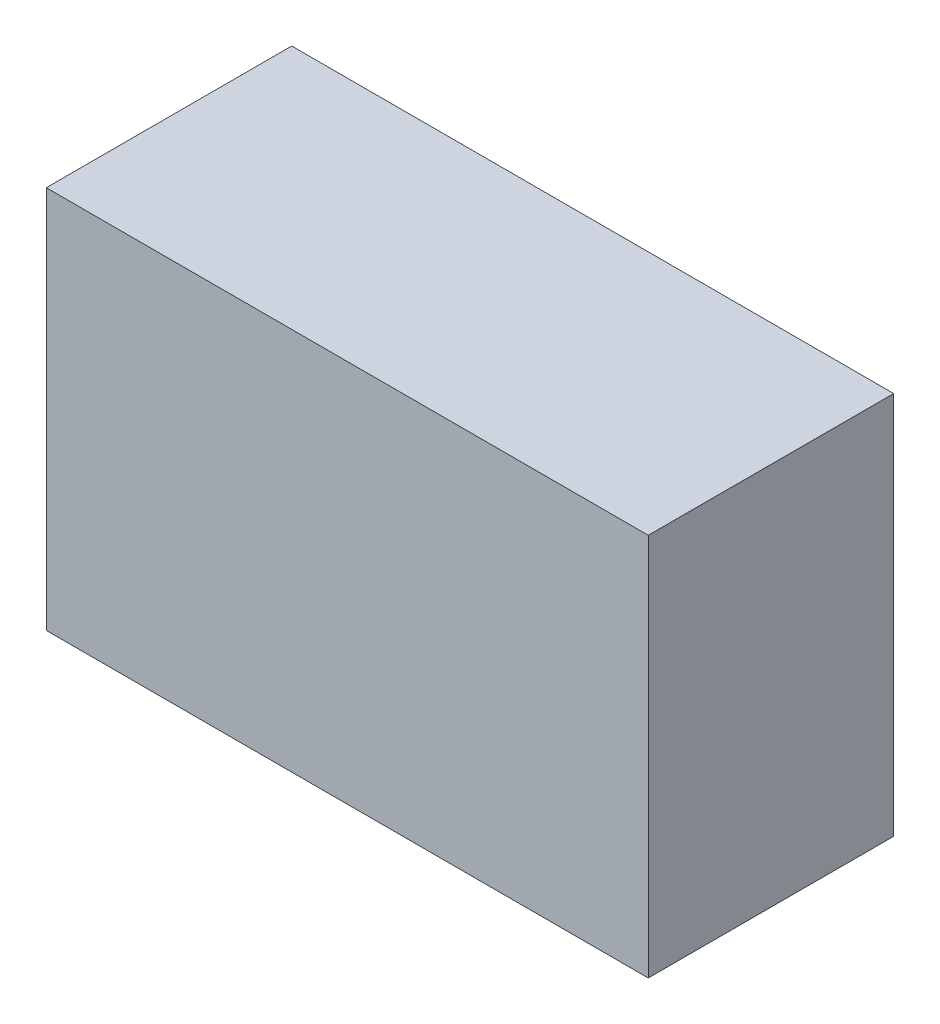
SolidWorks part; units mm, degrees
material "1060 Alloy"
ref_plane "Front" through (0, 0, 0) normal (0, 0, 1) x (1, 0, 0)
ref_plane "Top" through (0, 0, 0) normal (0, 1, 0) x (1, 0, 0)
ref_plane "Right" through (0, 0, 0) normal (1, 0, 0) x (0, 0, -1)
sketch "Sketch3" plane through (0, 0, 0) normal (0, 0, 1) x (1, 0, 0)
  line L0 (-0.127, -6.35) -> (30.1755, -6.35)
  line L1 (0, 0) -> (31.1484, 0)
  line L2 (0, 0) -> (0, -19.8376)
  line L3 (0, -19.8376) -> (31.1484, -19.8376)
  line L4 (31.1484, 0) -> (31.1484, -19.8376)
  line L5 (15.5742, -19.8376) -> (15.5742, 0) construction
  line L6 (15.5742, -6.35) -> (8.0621, -19.3614) construction
  line L15 (12.5496, -11.5887) -> (15.5742, -13.335) construction
  line L16 (15.5742, -6.35) -> (22.9274, -19.0862) construction
  circle A0 centre (15.5742, -6.35) radius 6.0492 construction
  point P14 (0, -6.35)
  point P17 (9.525, -6.35)
  point P19 (31.1484, -6.35)
  point P20 (7.7871, -19.8376)
  point P24 (23.3613, -19.8376)
  dimension "D2" = 6.35
  dimension "D6" = 3.4925
  dimension "D3" = 60
  dimension "D1" = 9.525
  dimension "D4" = 9.525
  dimension "D5" = 60
extrude "Boss-Extrude1" add sketch "Sketch3" along normal mid plane 12.7
sketch "Sketch4" plane through (0, 0, 0) normal (-1, 0, 0) x (0, 0, 1)
  circle A0 centre (0, -6.35) radius 3.175
  dimension "D1" = 6.35
extrude "Cut-Extrude1" cut sketch "Sketch4" against normal blind 9.525
ref_plane "Plane1" through (7.7871, -19.8376, 0) normal (-0.5, -0.866, 0) x (-0.866, 0.5, 0)
ref_plane "Mirror Plane" through (15.5742, 0, 0) normal (-1, 0, 0) x (0, 0, 1)
sketch "Sketch5" plane through (7.7871, -19.8376, 0) normal (-0.5, -0.866, 0) x (-0.866, 0.5, 0)
  circle A0 centre (0, 0) radius 3.175
  dimension "D1" = 6.35
extrude "Cut-Extrude5" cut sketch "Sketch5" against normal blind 9.525 and the other way up to next
sketch "Sketch6" plane through (0, 0, -6.35) normal (0, 0, -1) x (-1, 0, 0)
  circle A0 centre (-15.5742, -6.35) radius 3.175
  dimension "D1" = 6.35
extrude "Cut-Extrude6" cut sketch "Sketch6" against normal blind 9.525
mirror "Mirror1" about plane through (15.5742, 0, 0) normal (-1, 0, 0) of "Cut-Extrude5"
equation "\"truss_member_od\" = .25in"
equation "\"truss_member_id\" = 0in"
equation "\"truss_member_L1\" = 2.75in"
equation "\"connector_hole_depth\" = .375in"
equation "\"D1@Boss-Extrude1\"=\"truss_member_od\"*2"
equation "\"D6@Sketch3\"=\"truss_member_od\"/2*1.1"
equation "\"D1@Sketch4\"=\"truss_member_od\""
equation "\"D1@Cut-Extrude1\"=\"connector_hole_depth\""
equation "\"D1@Sketch3\"=\"connector_hole_depth\""
equation "\"D4@Sketch3\"=\"connector_hole_depth\""
equation "\"D1@Sketch5\"=\"truss_member_od\""
equation "\"D1@Cut-Extrude5\"=\"connector_hole_depth\""
equation "\"D1@Cut-Extrude6\"=\"connector_hole_depth\""
equation "\"D1@Sketch6\"=\"truss_member_od\""
